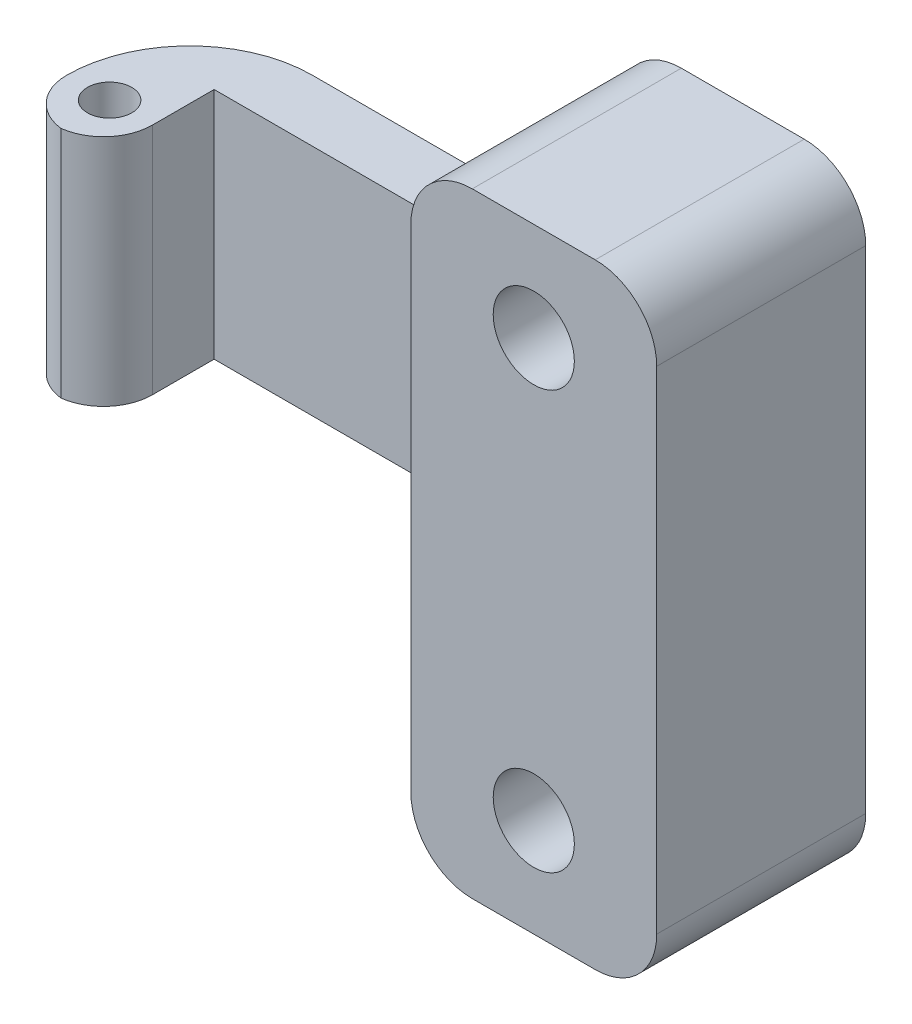
SolidWorks part; units mm, degrees
ref_plane "Přední rovina" through (0, 0, 0) normal (0, 0, 1) x (1, 0, 0)
ref_plane "Horní rovina" through (0, 0, 0) normal (0, 1, 0) x (1, 0, 0)
ref_plane "Pravá rovina" through (0, 0, 0) normal (1, 0, 0) x (0, 0, -1)
sketch "Base sketch" plane through (0, 0, 0) normal (0, 0, 1) x (1, 0, 0)
  line L1 (-17.5, 9.5) -> (17.5, 9.5)
  line L2 (-17.5, 9.5) -> (-17.5, -9.5)
  line L3 (-17.5, -9.5) -> (17.5, -9.5)
  line L4 (17.5, 9.5) -> (17.5, -9.5)
  line L5 (-17.5, 9.5) -> (17.5, -9.5) construction
  line L6 (-17.5, -9.5) -> (17.5, 9.5) construction
  line L7 (37.5, 25) -> (17.5, 25)
  line L8 (37.5, 25) -> (37.5, -25)
  line L9 (37.5, -25) -> (17.5, -25)
  line L10 (17.5, 25) -> (17.5, -25)
  line L11 (37.5, 25) -> (17.5, -25) construction
  line L12 (37.5, -25) -> (17.5, 25) construction
  point P0 (0, 0)
  point P6 (27.5, 0)
  point P11 (37.5, 0)
  point P12 (17.5, 0)
  dimension "D1" = 19
  dimension "D2" = 35
  dimension "D3" = 50
  dimension "D4" = 20
extrude "Base" add sketch "Base sketch" along normal blind 5 contours L4 L1 L2 L3 | L7 L10 L4 L9 L8 region at (0, 0, 0) region at (27.5, 0, 0)
sketch "Hinge sketch" plane through (0, 0, 5) normal (0, 0, 1) x (1, 0, 0)
  line L0 (-17.5, -9.5) -> (17.5, -9.5) construction
  line L1 (-17.5, 9.5) -> (-10.5, 9.5)
  line L2 (-17.5, 9.5) -> (-17.5, -9.5)
  line L3 (-17.5, -9.5) -> (-10.5, -9.5)
  line L4 (-10.5, 9.5) -> (-10.5, -9.5)
  dimension "D1" = 7
extrude "Hinge body" add sketch "Hinge sketch" along normal blind 9
sketch "Hinge hole sketch" plane through (0, -9.5, 0) normal (0, -1, 0) x (1, 0, 0)
  line L0 (-14, 14) -> (-14, 0)
  line L1 (-17.5, 14) -> (-10.5, 14) construction
  line L2 (-17.5, 0) -> (17.5, 0) construction
  point P6 (-14, 10)
  dimension "D1" = 4
hole_wizard "Hinge hole" positions "Skica4" profile "Skica5" hole size "M3" standard "DIN" end condition up to next
sketch "Skica4" plane through (0, -9.5, 0) normal (0, -1, 0) x (-1, 0, 0)
  point P0 (14, -10)
sketch "Skica5" plane through (-14, -9.5, 10) normal (1, 0, 0) x (0, 0, -1)
  line L0 (0, 0) -> (0, 19)
  line L1 (0, 19) -> (1.8, 19)
  line L2 (1.8, 19) -> (1.8, 0)
  line L5 (1.8, 0) -> (0, 0)
  line L11 (0, -6.35) -> (0, 107.95) construction
  dimension "Průměr díry skrz" = 3.6
  dimension "Hloubka díry skrz" = 19
sketch "Door body sketch" plane through (0, 0, 5) normal (0, 0, 1) x (1, 0, 0)
  line L1 (17.5, 25) -> (37.5, 25)
  line L2 (17.5, 25) -> (17.5, -25)
  line L3 (17.5, -25) -> (37.5, -25)
  line L4 (37.5, 25) -> (37.5, -25)
extrude "Door body" add sketch "Door body sketch" along normal blind 12
sketch "Door screws sketch" plane through (0, 0, 0) normal (0, 0, -1) x (-1, 0, 0)
  line L0 (-27.5, 25) -> (-27.5, -25)
  line L1 (-37.5, 25) -> (-17.5, 25) construction
  line L2 (-37.5, -25) -> (-17.5, -25) construction
  point P6 (-27.5, 17)
  point P7 (-27.5, -17)
  dimension "D1" = 8
  dimension "D2" = 8
hole_wizard "Door screws" positions "Skica8" profile "Skica9" counterbore size "M6" standard "DIN" end condition up to next
sketch "Skica8" plane through (0, 0, 0) normal (0, 0, -1) x (-1, 0, 0)
  point P0 (-27.5, 17)
  point P3 (-27.5, -17)
sketch "Skica9" plane through (27.5, 17, 0) normal (1, 0, 0) x (0, 1, 0)
  line L0 (0, 0) -> (0, 17)
  line L1 (0, 17) -> (3.3, 17)
  line L3 (3.3, 17) -> (3.3, 6.4)
  line L4 (3.3, 6.4) -> (5.5, 6.4)
  line L5 (5.5, 6.4) -> (5.5, 0)
  line L7 (5.5, 0) -> (0, 0)
  line L11 (0, -6.35) -> (0, 107.95) construction
  dimension "Průměr díry skrz" = 6.6
  dimension "Hloubka díry skrz" = 17
  dimension "Průměr válcového zahloubení" = 11
  dimension "Hloubka válcového zahloubení" = 6.4
fillet "Hinge round" radius 3.99 2 edges at (-17.5, 0, 14) (-10.5, 0, 14)
fillet "Hinge body round" radius 10 1 edges at (-17.5, 0, 0)
fillet "Door corners round" radius 5 4 edges at (17.5, 25, 8.5) (37.5, 25, 8.5) (37.5, -25, 8.5) (17.5, -25, 8.5)
fillet "Door body line" radius 3 2 edges at (17.5, -9.5, 2.5) (17.5, 9.5, 2.5)
